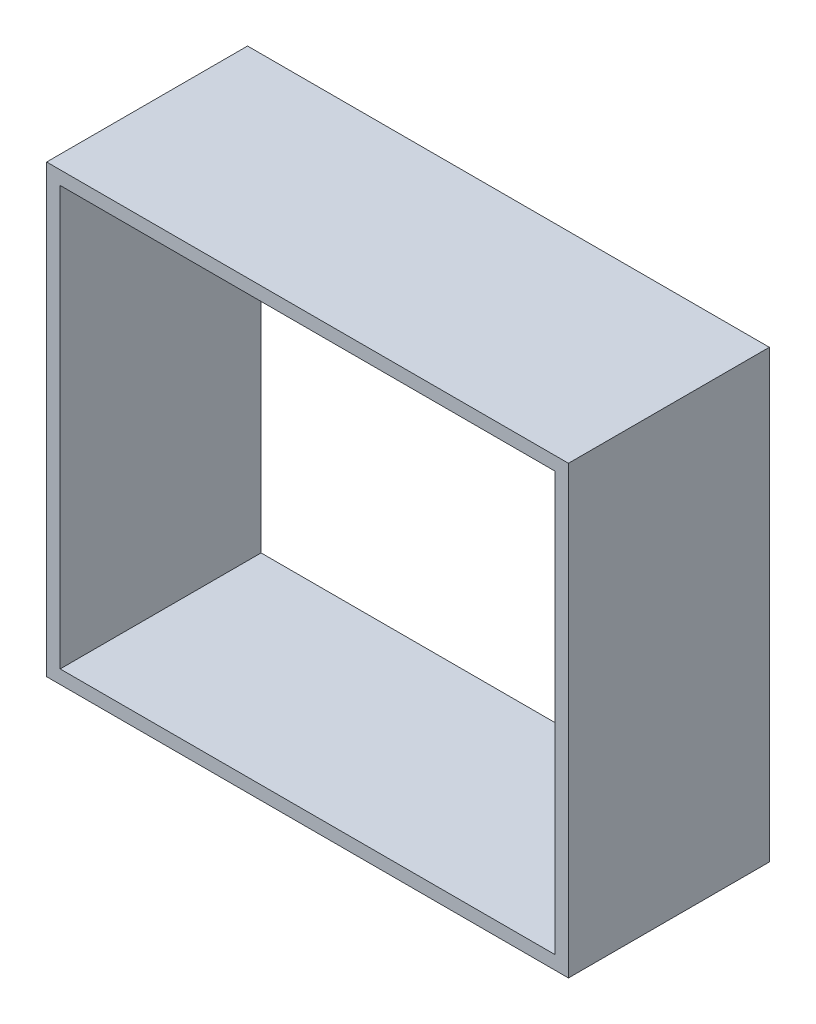
SolidWorks part; units mm, degrees
ref_plane "Спереди" through (0, 0, 0) normal (0, 0, 1) x (1, 0, 0)
ref_plane "Сверху" through (0, 0, 0) normal (0, 1, 0) x (1, 0, 0)
ref_plane "Справа" through (0, 0, 0) normal (1, 0, 0) x (0, 0, -1)
sketch "Эскиз1" plane through (0, 0, 0) normal (0, 0, 1) x (1, 0, 0)
  line L0 (28.448, -30.734) -> (-28.448, -30.734) construction
  line L1 (-36.648, -30.934) -> (36.4562, -30.934)
  line L2 (-36.648, -30.934) -> (-36.648, 30.934)
  line L3 (-36.648, 30.934) -> (36.4562, 30.934)
  line L4 (36.4562, -30.934) -> (36.4562, 30.934)
  line L5 (-28.448, 30.734) -> (28.448, 30.734) construction
  line L6 (36.2562, 10.4902) -> (36.2562, -10.4902) construction
  line L8 (-38.648, -32.934) -> (38.4562, -32.934)
  line L9 (38.4562, -32.934) -> (38.4562, 32.934)
  line L10 (-38.648, 32.934) -> (38.4562, 32.934)
  line L11 (-38.648, -32.934) -> (-38.648, 32.934)
  line L12 (-36.448, 9.1) -> (-36.448, -9.1) construction
  point P0 (0, 0)
  point P8 (-35.2613, 36.5389)
  point P9 (-39.8086, 30.934)
  point P16 (37.7975, 34.194)
  dimension "D1" = 0.2
  dimension "D2" = 0.2
  dimension "D4" = 0.2
  dimension "D5" = 0.2
  dimension "D3" = 2
extrude "Бобышка-Вытянуть1" add sketch "Эскиз1" along normal up to surface (29.687 mm away)
